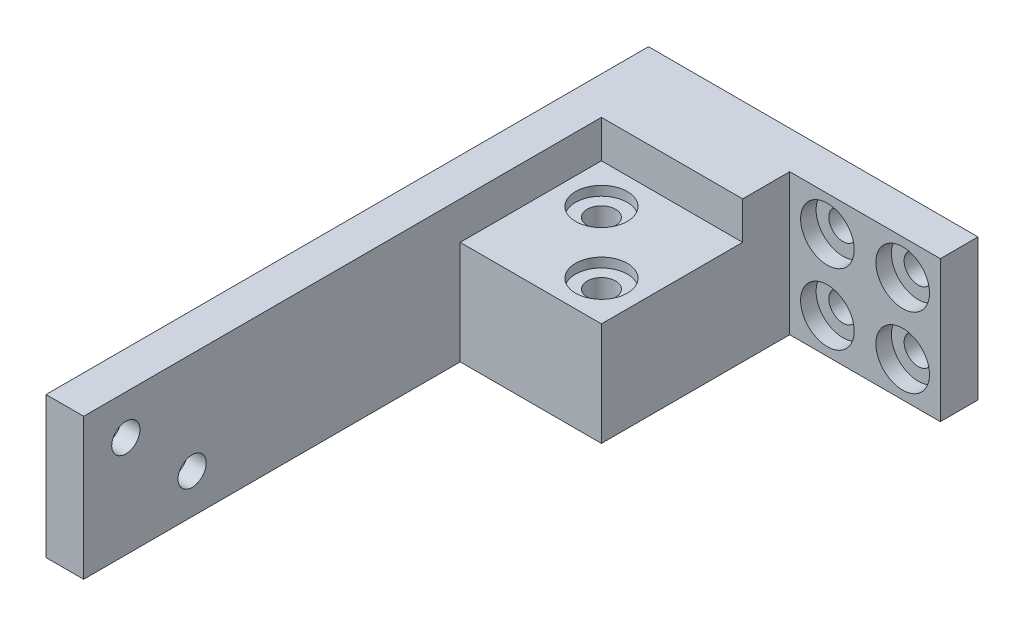
SolidWorks part; units mm, degrees
note: The reader was unsure of these and kept them because the rebuilt part matched: shared geometry of "Croquis4<3>", "Croquis11<3>".
ref_plane "Alzado" through (0, 0, 0) normal (0, 0, 1) x (1, 0, 0)
ref_plane "Planta" through (0, 0, 0) normal (0, 1, 0) x (1, 0, 0)
ref_plane "Vista lateral" through (0, 0, 0) normal (1, 0, 0) x (0, 0, -1)
sketch "Croquis1" plane through (0, 0, 0) normal (0, 0, 1) x (1, 0, 0)
  line L0 (19, 0) -> (35, 0)
  line L5 (19, 15) -> (35, 15)
  line L20 (4, 15) -> (19, 0) construction
  line L21 (4, 0) -> (19, 15) construction
  line L22 (0, 15) -> (4, 0) construction
  line L23 (0, 0) -> (4, 15) construction
  line L24 (19, 7.5) -> (35, 7.5) construction
  line L25 (19, 0) -> (19, 15)
  line L26 (4, 15) -> (19, 15)
  line L27 (4, 0) -> (4, 15)
  line L28 (4, 0) -> (19, 0)
  line L29 (4, 0) -> (4, 15)
  line L30 (0, 15) -> (4, 15)
  line L31 (0, 0) -> (0, 15)
  line L32 (0, 0) -> (4, 0)
  line L33 (35, 15) -> (35, 0)
  line L35 (0, 15) -> (0, 0)
  circle A4 centre (31, 11.25) radius 1.5
  circle A5 centre (31, 3.75) radius 1.5
  circle A6 centre (23, 11.25) radius 1.5
  circle A7 centre (23, 3.75) radius 1.5
  point P43 (17.0691, 10.6256)
  point P44 (7.5691, 10.6256)
  dimension "D3" = 35
  dimension "D9" = 4
  dimension "D5" = 3
  dimension "D1" = 4
  dimension "D2" = 15
  dimension "D4" = 15
  dimension "D6" = 3.75
  dimension "D7" = 4
  dimension "D8" = 3.75
extrude "Saliente-Extruir1" add sketch "Croquis1" along normal blind 4 contours L27 L28 L25 L26 | L31 L32 L27 L30 | L33 L5 L25 L0 A6 A4 A5 A7
sketch "Croquis2" plane through (0, 0, 4) normal (0, 0, 1) x (1, 0, 0)
  line L0 (0, 0) -> (35, 0) construction
  line L1 (0, 15) -> (4, 15)
  line L2 (0, 15) -> (0, 0)
  line L3 (0, 0) -> (4, 0)
  line L4 (4, 15) -> (4, 0)
  line L5 (0, 15) -> (4, 0) construction
  line L6 (0, 0) -> (4, 15) construction
  point P4 (2, 7.5)
  dimension "D1" = 4
extrude "Saliente-Extruir2" add sketch "Croquis2" along normal blind 60
sketch "Croquis3" plane through (0, 0, 4) normal (0, 0, 1) x (1, 0, 0)
  line L1 (4, 15) -> (19, 15)
  line L2 (4, 15) -> (4, 0)
  line L3 (4, 0) -> (19, 0)
  line L4 (19, 15) -> (19, 0)
  line L5 (4, 15) -> (19, 0) construction
  line L6 (4, 0) -> (19, 15) construction
  line L7 (4, 0) -> (35, 0) construction
  point P4 (11.5, 7.5)
  dimension "D1" = 15
extrude "Saliente-Extruir3" add sketch "Croquis3" along normal blind 20
sketch "Croquis9" plane through (0, 0, 4) normal (0, 0, 1) x (1, 0, 0)
  circle A0 centre (23, 3.75) radius 2.85
  circle A1 centre (31, 3.75) radius 2.85
  circle A2 centre (23, 11.25) radius 2.85
  circle A3 centre (31, 11.25) radius 2.85
  dimension "D1" = 5.7
extrude "Cortar-Extruir3" cut sketch "Croquis9" against normal blind 1.65
sketch "Croquis4" plane through (0, 0, 0) normal (1, 0, 0) x (0, 0, -1)
  line L0 (-64, 0) -> (-24, 0) construction
  line L5 (-64, 0) -> (0, 0) construction
  line L6 (-64, 15) -> (-48, 15)
  line L7 (-64, 15) -> (-64, 0)
  line L8 (-64, 0) -> (-48, 0)
  line L9 (-48, 15) -> (-48, 0)
  line L10 (-64, 15) -> (-48, 0) construction
  line L11 (-64, 0) -> (-48, 15) construction
  line L12 (-55.23, 5.7877) -> (-55.23, 2.6123)
  line L13 (-55.23, 2.6123) -> (-52.48, 1.0246)
  line L14 (-52.48, 1.0246) -> (-49.73, 2.6123)
  line L15 (-49.73, 2.6123) -> (-49.73, 5.7877)
  line L16 (-49.73, 5.7877) -> (-52.48, 7.3754)
  line L17 (-52.48, 7.3754) -> (-55.23, 5.7877)
  line L18 (-62.27, 12.3877) -> (-62.27, 9.2123)
  line L19 (-62.27, 9.2123) -> (-59.52, 7.6246)
  line L20 (-59.52, 7.6246) -> (-56.77, 9.2123)
  line L21 (-56.77, 9.2123) -> (-56.77, 12.3877)
  line L22 (-56.77, 12.3877) -> (-59.52, 13.9754)
  line L23 (-59.52, 13.9754) -> (-62.27, 12.3877)
  circle A1 centre (-59.52, 10.8) radius 1.5
  circle A2 centre (-52.48, 4.2) radius 1.5
  circle A5 centre (-52.48, 4.2) radius 2.75 construction
  circle A6 centre (-59.52, 10.8) radius 2.75 construction
  point P4 (-56, 7.5)
  dimension "D2" = 3
  dimension "D1" = 16
  dimension "D6" = 5.5
  dimension "D3" = 4.2
  dimension "D4" = 4.2
  dimension "D7" = 5.5
extrude "Cortar-Extruir4" cut sketch "Croquis4" along normal up to next contours A1 | A2
extrude "Cortar-Extruir5" cut sketch "Croquis4<3>" along normal blind 2 contours L23 L22 L21 L20 L19 L18 A1 | L17 L16 L15 L14 L13 L12 A2
sketch "Croquis4<3>" plane through (0, 0, 0) normal (1, 0, 0) x (0, 0, -1) same geometry as "Croquis4"
sketch "Croquis10" plane through (0, 15, 0) normal (0, 1, 0) x (1, 0, 0)
  line L1 (19, -24) -> (4, -24)
  line L2 (19, -24) -> (19, -9)
  line L3 (19, -9) -> (4, -9)
  line L4 (4, -24) -> (4, -9)
  line L5 (19, -24) -> (4, -9) construction
  line L6 (19, -9) -> (4, -24) construction
  point P4 (11.5, -16.5)
  dimension "D1" = 15
extrude "Cortar-Extruir6" cut sketch "Croquis10" against normal blind 4
sketch "Croquis11" plane through (0, 11, 0) normal (0, 1, 0) x (1, 0, 0)
  line L1 (19, -24) -> (4, -24)
  line L2 (19, -24) -> (19, -9)
  line L3 (19, -9) -> (4, -9)
  line L4 (4, -24) -> (4, -9)
  line L5 (19, -24) -> (4, -9) construction
  line L6 (19, -9) -> (4, -24) construction
  circle A0 centre (14.8, -19.8) radius 1.5
  circle A1 centre (8.2, -13.2) radius 1.5
  circle A2 centre (14.8, -19.8) radius 2.75
  circle A3 centre (8.2, -13.2) radius 2.75
  point P5 (11.5, -16.5)
  dimension "D1" = 5.5
  dimension "D2" = 5.5
  dimension "D5" = 3
  dimension "D6" = 3
  dimension "D3" = 4.2
  dimension "D4" = 4.2
extrude "Cortar-Extruir7" cut sketch "Croquis11" against normal blind 6 contours A0 | A1
extrude "Cortar-Extruir8" cut sketch "Croquis11<3>" against normal blind 1
sketch "Croquis11<3>" plane through (0, 11, 0) normal (0, 1, 0) x (1, 0, 0) same geometry as "Croquis11"
